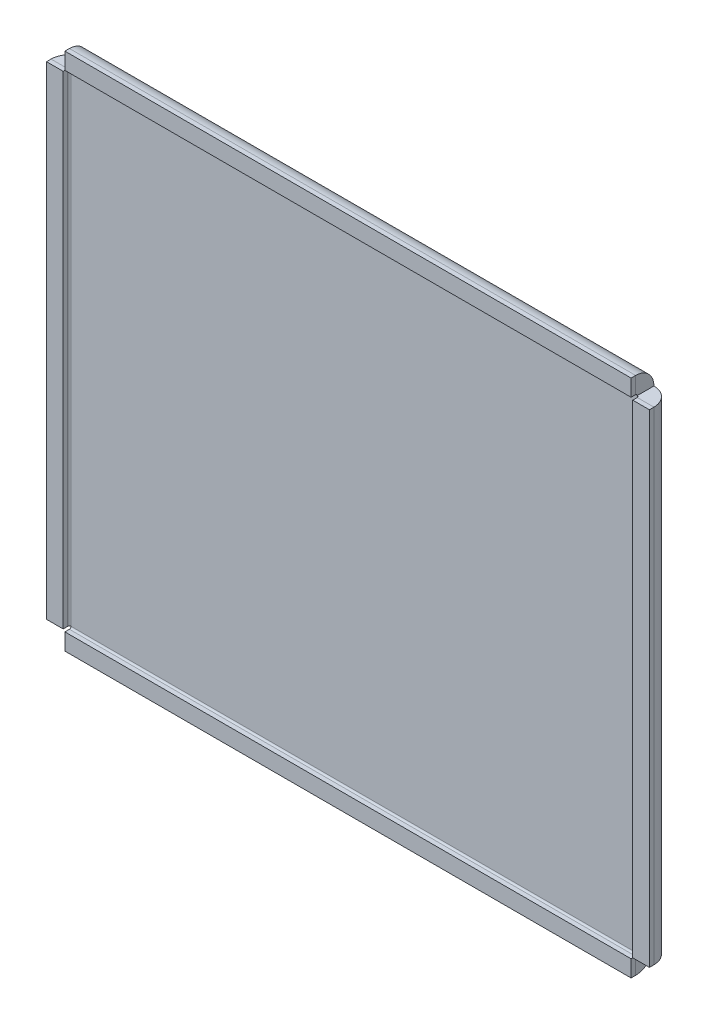
SolidWorks part; units mm, degrees
note: The reader was unsure of these and kept them because the rebuilt part matched: thickness of "Base-Flange1", "Edge-Flange1", "Edge-Flange2", "Edge-Flange3", "Edge-Flange4"; flange length of "Edge-Flange1", "Edge-Flange2", "Edge-Flange3", "Edge-Flange4".
ref_plane "front" through (0, 0, 0) normal (0, 0, 1) x (1, 0, 0)
ref_plane "top" through (0, 0, 0) normal (0, 1, 0) x (1, 0, 0)
ref_plane "right" through (0, 0, 0) normal (1, 0, 0) x (0, 0, -1)
sketch "Sketch1" plane through (0, 0, 0) normal (0, 0, 1) x (1, 0, 0)
  line L1 (-215.9, 184.15) -> (215.9, 184.15)
  line L2 (-215.9, 184.15) -> (-215.9, -184.15)
  line L3 (-215.9, -184.15) -> (215.9, -184.15)
  line L4 (215.9, 184.15) -> (215.9, -184.15)
  point P4 (0, 184.15)
  point P5 (215.9, 0)
  dimension "D1" = 431.8
  dimension "D2" = 368.3
sheet metal parameters "Sheet-Metal1" thickness 12.7 parameters "D1"=1.27
base flange "Base-Flange1" sketch "Sketch1" thickness 12.7 reverse thickness direction yes parameters "D1"=1.27
edge flange "Edge-Flange1" sketch "Sketch5" flange angle 90 flange length 4.7244 flange position bend outside bend radius 1.27 thickness 12.7 relief rectangular parameters "D6"=10
sketch "Sketch5" plane through (0, 184.15, 12.7) normal (0, -1, 0) x (1, 0, 0)
  line L1 (215.9, 0) -> (-215.9, 0) construction
  line L2 (215.9, 0) -> (215.9, 4.7244)
  line L3 (215.9, 4.7244) -> (-215.9, 4.7244)
  line L4 (-215.9, 4.7244) -> (-215.9, 0)
  line L5 (215.9, 0) -> (-215.9, 0)
bend "EdgeBend1" bend radius 1.27 bend angle 90 parameters "D5"=1
edge flange "Edge-Flange2" sketch "Sketch8" flange angle 90 flange length 4.7244 flange position bend outside bend radius 1.27 thickness 12.7 relief rectangular parameters "D6"=10
sketch "Sketch8" plane through (0, -184.15, 12.7) normal (0, -1, 0) x (1, 0, 0)
  line L2 (-215.9, 0) -> (-215.9, 4.7244)
  line L3 (-215.9, 4.7244) -> (215.9, 4.7244)
  line L4 (215.9, 4.7244) -> (215.9, 0)
  line L5 (-215.9, 0) -> (215.9, 0) construction
  line L6 (-215.9, 0) -> (215.9, 0)
bend "EdgeBend2" bend radius 1.27 bend angle 90 parameters "D5"=2
edge flange "Edge-Flange3" sketch "Sketch12" flange angle 90 flange length 4.7244 flange position bend outside bend radius 1.27 thickness 12.7 relief rectangular parameters "D6"=10
sketch "Sketch12" plane through (215.9, 0, 12.7) normal (-1, 0, 0) x (0, -1, 0)
  line L2 (-184.15, 0) -> (-184.15, 4.7244)
  line L3 (-184.15, 4.7244) -> (184.15, 4.7244)
  line L4 (184.15, 4.7244) -> (184.15, 0)
  line L6 (184.15, 0) -> (-184.15, 0) construction
  line L7 (184.15, 0) -> (-184.15, 0)
bend "EdgeBend3" bend radius 1.27 bend angle 90 parameters "D5"=3
edge flange "Edge-Flange4" sketch "Sketch15" flange angle 90 flange length 4.7244 flange position bend outside bend radius 1.27 thickness 12.7 relief rectangular parameters "D6"=10
sketch "Sketch15" plane through (-215.9, 0, 12.7) normal (1, 0, 0) x (0, 1, 0)
  line L2 (-184.15, 0) -> (-184.15, 4.7244)
  line L3 (-184.15, 4.7244) -> (184.15, 4.7244)
  line L4 (184.15, 4.7244) -> (184.15, 0)
  line L6 (184.15, 0) -> (-184.15, 0) construction
  line L7 (184.15, 0) -> (-184.15, 0)
bend "EdgeBend4" bend radius 1.27 bend angle 90 parameters "D5"=4
flat pattern "Flat-Pattern1"
sketch "Bend-Lines1" plane through (0, 0, 12.7) normal (0, 0, 1) x (1, 0, 0)
  line L0 (215.9, -195.122) -> (-215.9, -195.122) construction
  line L1 (-215.9, 195.122) -> (215.9, 195.122) construction
  line L2 (215.9, -195.122) -> (-215.9, -195.122) construction
  line L3 (-215.9, 195.122) -> (215.9, 195.122) construction
  line L4 (-226.872, -184.15) -> (-226.872, 184.15) construction
  line L5 (226.872, 184.15) -> (226.872, -184.15) construction
  line L6 (-226.872, -184.15) -> (-226.872, 184.15) construction
  line L7 (226.872, 184.15) -> (226.872, -184.15) construction
bend of the flat pattern "Flatten-<EdgeBend1>1"
bend of the flat pattern "Flatten-<EdgeBend2>1"
bend of the flat pattern "Flatten-<EdgeBend3>1"
bend of the flat pattern "Flatten-<EdgeBend4>1"
